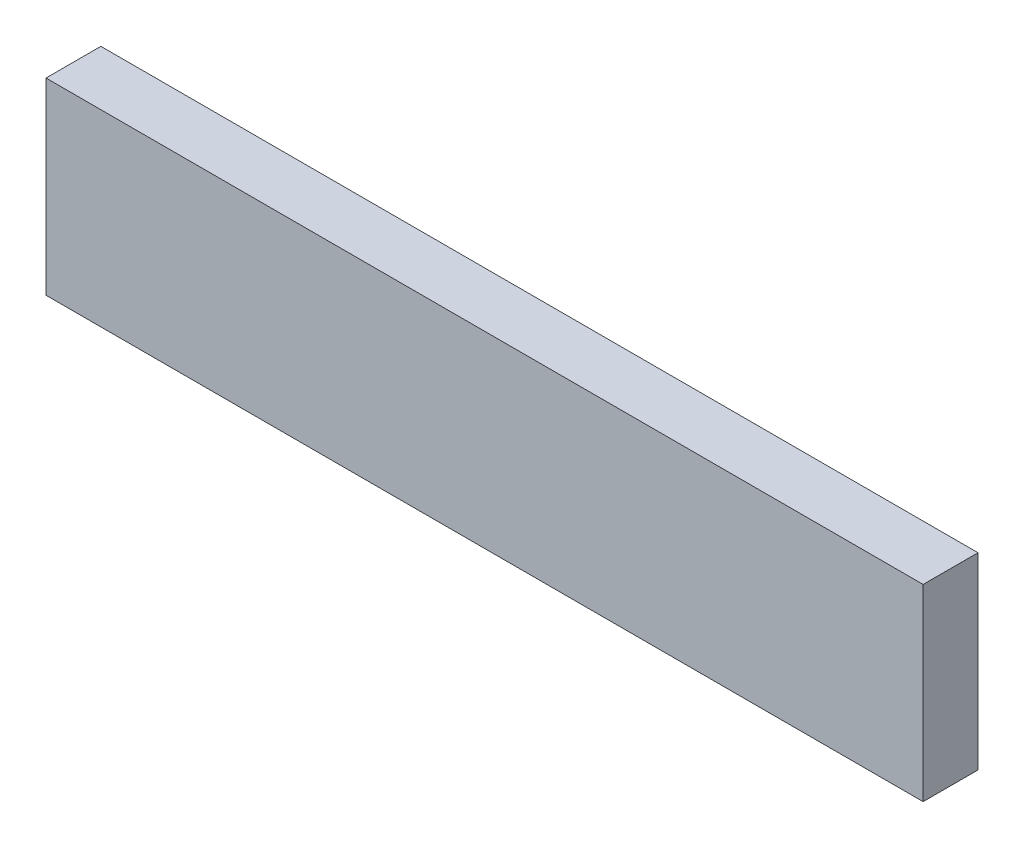
SolidWorks part; units mm, degrees
ref_plane "Front Plane" through (0, 0, 0) normal (0, 0, 1) x (1, 0, 0)
ref_plane "Top Plane" through (0, 0, 0) normal (0, 1, 0) x (1, 0, 0)
ref_plane "Right Plane" through (0, 0, 0) normal (1, 0, 0) x (0, 0, -1)
sketch "Sketch1" plane through (0, 0, 0) normal (0, 1, 0) x (1, 0, 0)
  line L1 (-177.6251, -11.1125) -> (177.6251, -11.1125)
  line L2 (-177.6251, -11.1125) -> (-177.6251, 11.1125)
  line L3 (-177.6251, 11.1125) -> (177.6251, 11.1125)
  line L4 (177.6251, -11.1125) -> (177.6251, 11.1125)
  line L5 (-177.6251, -11.1125) -> (177.6251, 11.1125) construction
  line L6 (-177.6251, 11.1125) -> (177.6251, -11.1125) construction
  point P0 (0, 0)
extrude "Boss-Extrude1" add sketch "Sketch1" along normal mid plane 76.2 contours L1 L4 L3 L2
sketch "Sketch2" plane through (0, 38.1, 0) normal (0, 1, 0) x (1, 0, 0)
  line L1 (-177.6251, -11.1125) -> (-177.6251, 11.1125) construction
  line L2 (-177.6251, 1.5875) -> (177.6251, 1.5875)
  line L3 (177.6251, -11.1125) -> (177.6251, 11.1125) construction
  line L4 (-177.6251, -4.7625) -> (177.6251, -4.7625)
